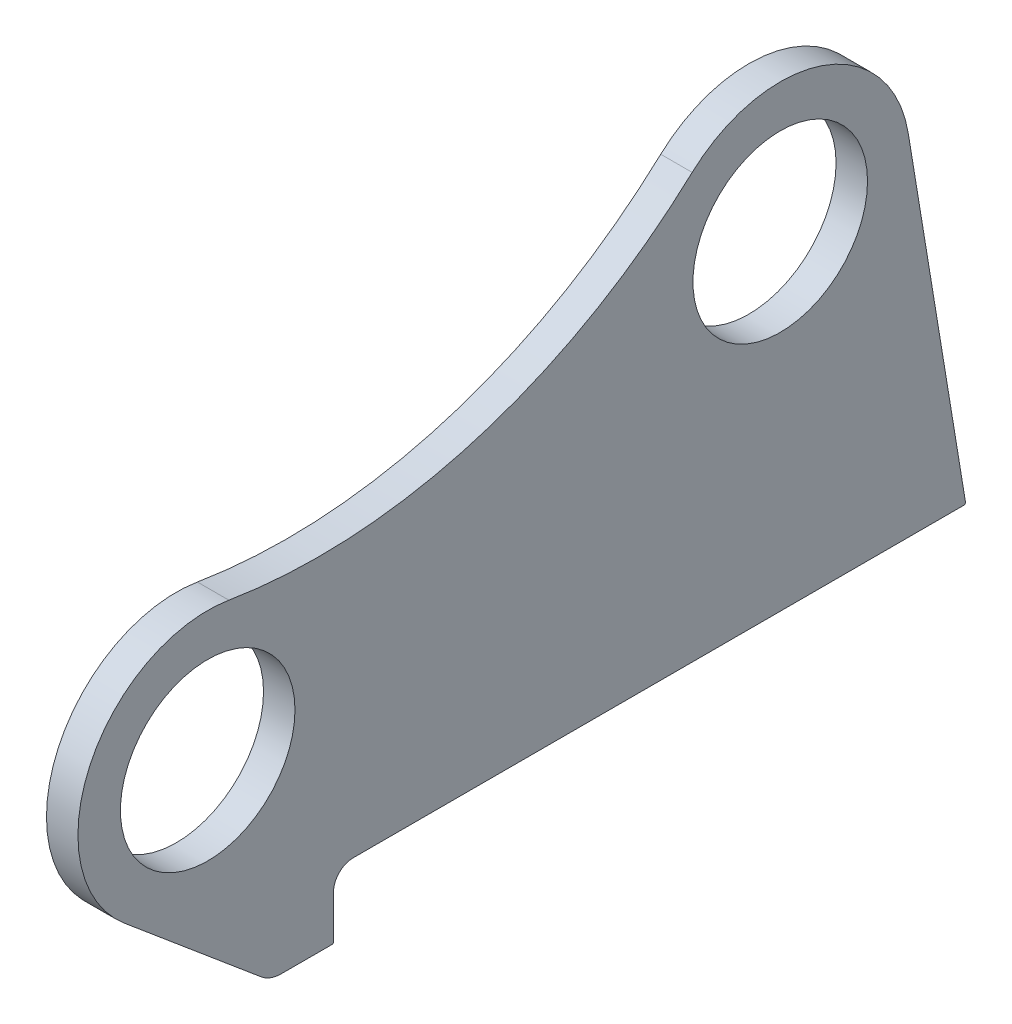
SolidWorks part; units mm, degrees
material "MS-Grade 350"
ref_plane "Front Plane" through (0, 0, 0) normal (0, 0, 1) x (1, 0, 0)
ref_plane "Top Plane" through (0, 0, 0) normal (0, 1, 0) x (1, 0, 0)
ref_plane "Right Plane" through (0, 0, 0) normal (1, 0, 0) x (0, 0, -1)
sketch "Sketch1" plane through (0, 0, 0) normal (1, 0, 0) x (0, 0, -1)
  line L0 (0, -41) -> (0, -12.5)
  line L1 (12.5, 0) -> (402, 0)
  line L3 (402, 0) -> (365.4271, 222.4236)
  line L4 (-133.0582, 36.825) -> (-45.9722, -36.3151)
  line L11 (0, -41) -> (-33.1096, -41)
  line L12 (-80, 100) -> (284.0202, 209.038) construction
  circle A0 centre (-80, 100) radius 55.5
  circle A1 centre (284.0202, 209.038) radius 55.5
  arc A2 (-66.5474, 181.3958) -> (-133.0582, 36.825) centre (-80, 100) ccw
  arc A4 (-45.9722, -36.3151) -> (-33.1096, -41) centre (-33.1096, -21) ccw
  arc A5 (0, -12.5) -> (12.5, 0) centre (12.5, -12.5) cw
  arc A9 (365.4271, 222.4236) -> (228.0354, 269.6346) centre (284.0202, 209.038) ccw
  arc A10 (-66.5474, 181.3958) -> (228.0354, 269.6346) centre (-9.4757, 526.7113) ccw
  point P31 (0, 0)
  dimension "D2" = 100
  dimension "D4" = 82.5
  dimension "D5" = 111
  dimension "D6" = 41
  dimension "D7" = 350
  dimension "D13" = 40.026
  dimension "D20" = 12.5
  dimension "D3" = 20
  dimension "D12" = 402
  dimension "D15" = 16.675
  dimension "D16" = 380
  dimension "D17" = 80
sheet metal parameters "Sheet-Metal1" thickness 20 parameters "D1"=92
base flange "Base-Flange1" sketch "Sketch1" thickness 20 reverse thickness direction no parameters "D1"=92
fillet "Fillet-1.0" radius 1 2 edges at (-10, 0, -402) (-10, -41, 0)
flat pattern "Flat-Pattern1" [suppressed]
sketch "Bend-Lines1" plane through (0, 0, 0) normal (0, 1, 0) x (1, 0, 0)
sketch3d "Bounding-Box1" [suppressed]
  line L0 (-159.6299, -579.154, 0) -> (414.8787, -520.584, 0) construction
  line L1 (-191.1408, -270.0661, 0) -> (383.3678, -211.4961, 0) construction
  line L2 (-159.6299, -579.154, 0) -> (-191.1408, -270.0661, 0) construction
  line L3 (414.8787, -520.584, 0) -> (383.3678, -211.4961, 0) construction
